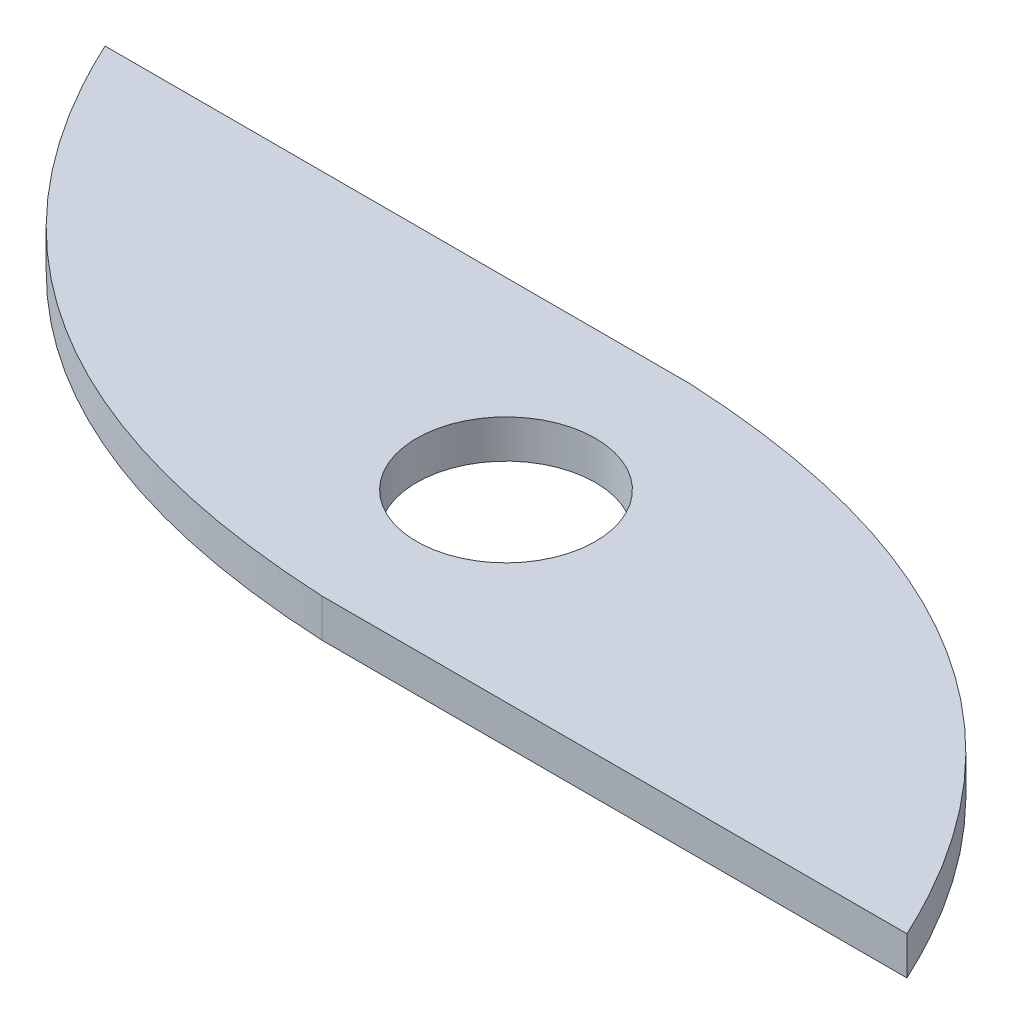
SolidWorks part; units mm, degrees
ref_plane "Front Plane" through (0, 0, 0) normal (0, 0, 1) x (1, 0, 0)
ref_plane "Top Plane" through (0, 0, 0) normal (0, 1, 0) x (1, 0, 0)
ref_plane "Right Plane" through (0, 0, 0) normal (1, 0, 0) x (0, 0, -1)
sketch "Sketch1" plane through (0, 0, 0) normal (0, 1, 0) x (1, 0, 0)
  line L0 (-76.2, 0) -> (76.2, 0) construction
  line L1 (0, 22.86) -> (-72.6902, 22.86)
  line L2 (0, -22.86) -> (72.6902, -22.86)
  circle A0 centre (0, 0) radius 22.86
  circle A1 centre (0, 0) radius 11.1125
  circle A2 centre (0, 0) radius 76.2 construction
  spline S0 degree 2 poles (0, -22.86) (-52.6802, -20.3191) (-72.6902, 22.86) knots 0 0 0 1 1 1
  spline S1 degree 2 poles (0, 22.86) (52.6802, 20.3191) (72.6902, -22.86) knots 0 0 0 1 1 1
  point P7 (0, 0)
  dimension "D1" = 45.72
  dimension "D2" = 22.225
  dimension "D3" = 152.4
  dimension "D4" = 19.05
  dimension "D5" = 19.05
extrude "Boss-Extrude3" add sketch "Sketch1" along normal blind 4.7625 contours S0 A0 L1 | S1 A0 L2 | S1 A0 S0 A1 region at (-38.9735, 0, -6.0982) region at (1.2963, 0, -22.1434) region at (38.9735, 0, 6.0982)
